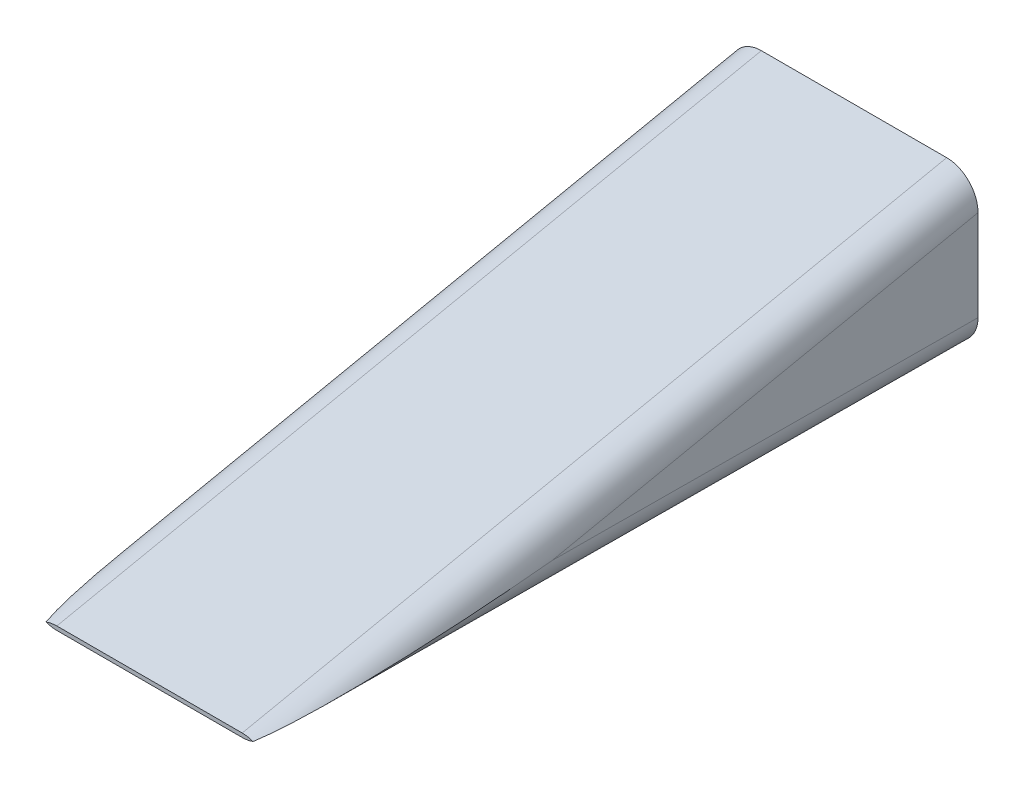
SolidWorks part; units mm, degrees
material "1.3# EPP"
ref_plane "Front Plane" through (0, 0, 0) normal (0, 0, 1) x (1, 0, 0)
ref_plane "Top Plane" through (0, 0, 0) normal (0, 1, 0) x (1, 0, 0)
ref_plane "Right Plane" through (0, 0, 0) normal (1, 0, 0) x (0, 0, -1)
sketch "Sketch1" plane through (0, 0, 0) normal (0, 0, 1) x (1, 0, 0)
  line L0 (16.3068, 8.6995) -> (-16.3068, 8.6995) construction
  line L1 (20.1168, 12.5095) -> (-20.1168, 12.5095)
  line L2 (20.1168, 12.5095) -> (20.1168, -12.5095)
  line L3 (20.1168, -12.5095) -> (-20.1168, -12.5095)
  line L4 (-20.1168, 12.5095) -> (-20.1168, -12.5095)
  line L5 (20.1168, 12.5095) -> (-20.1168, -12.5095) construction
  line L6 (20.1168, -12.5095) -> (-20.1168, 12.5095) construction
  line L7 (-16.3068, 8.6995) -> (-16.3068, -8.6995) construction
  line L8 (16.3068, -8.6995) -> (-16.3068, -8.6995) construction
  line L9 (16.3068, 8.6995) -> (16.3068, -8.6995) construction
  point P0 (0, 0)
  dimension "D1" = 25.019
  dimension "D2" = 40.2336
  dimension "D3" = 3.81
sketch3d "3DSketch1"
  line L1 (0, -6.8008, 114.3) -> (0, 49993.1992, 114.3) construction
  line L2 (0, 0, 114.3) -> (-50000, 0, 114.3) construction
  line L5 (-20.1168, -11.811, 114.3) -> (20.1168, -11.811, 114.3)
  line L6 (-20.1168, -11.811, 114.3) -> (-20.1168, -11.176, 114.3)
  line L7 (-20.1168, -11.176, 114.3) -> (20.1168, -11.176, 114.3)
  line L8 (20.1168, -11.811, 114.3) -> (20.1168, -11.176, 114.3)
  point P1 (0, -11.176, 114.3)
  dimension "D1" = 114.3
  dimension "D2" = 40.2336
  dimension "D3" = 0.635
  dimension "D4" = 11.176
loft "Loft1" add profiles "Sketch1", "3DSketch1" connector at (-20.1168, -12.5095, 0) connector at (-20.1168, -11.811, 114.3)
shell "Shell1" thickness 3.0734 removed face at (0, 0, 0)
fillet "Fillet1" radius 5.08 4 edges
